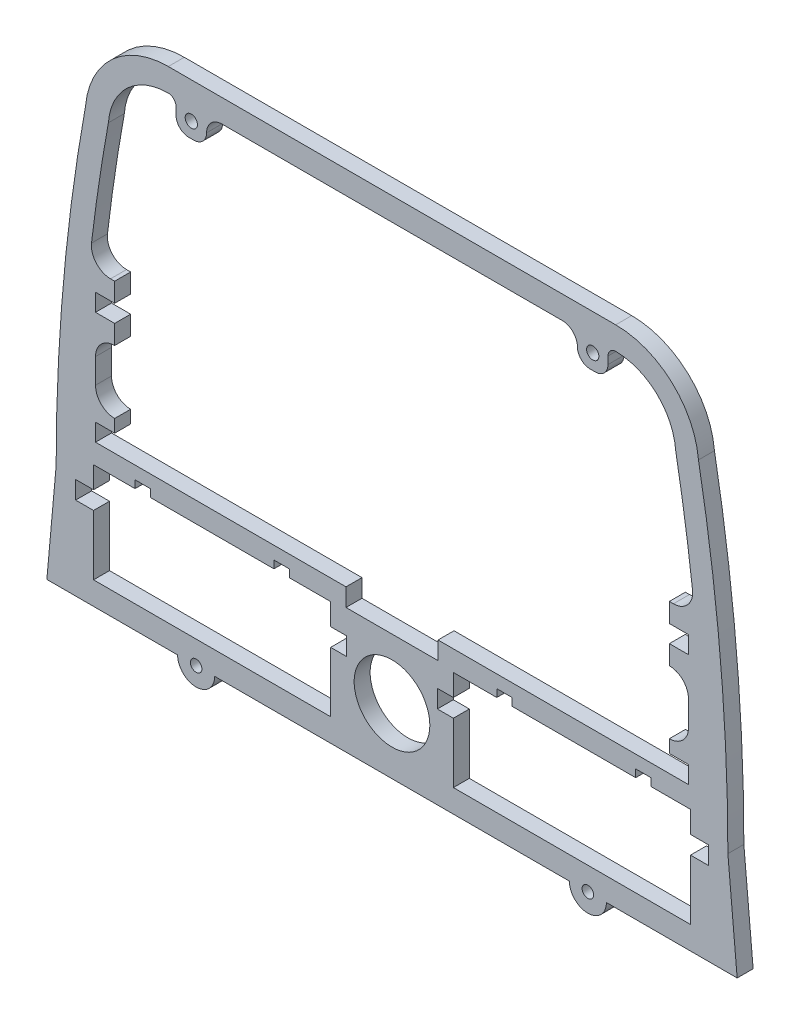
SolidWorks part; units mm, degrees
material "Delrin 2700 NC010, Low Viscosity Acetal Copolymer (SS)"
ref_plane "Front Plane" through (0, 0, 0) normal (0, 0, 1) x (1, 0, 0)
ref_plane "Top Plane" through (0, 0, 0) normal (0, 1, 0) x (1, 0, 0)
ref_plane "Right Plane" through (0, 0, 0) normal (1, 0, 0) x (0, 0, -1)
sketch "Sketch1" plane through (0, 0, 0) normal (0, 0, 1) x (1, 0, 0)
  line L0 (33.3676, -11.9888) -> (34.29, -22.225)
  line L1 (22.225, 27.94) -> (-22.225, 27.94)
  line L2 (-34.29, -22.225) -> (-30.4467, 20.4259) construction
  line L3 (-33.3676, -11.9888) -> (-33.3676, 14.6458) construction
  line L4 (-33.3676, -11.9888) -> (-34.29, -22.225)
  line L5 (16.9079, 25.654) -> (-16.9079, 25.654)
  line L6 (6.096, -13.97) -> (6.096, -19.939)
  line L7 (-29.6529, -19.939) -> (-6.096, -19.939)
  line L8 (-34.29, -22.225) -> (-21.299, -22.225)
  line L9 (-29.6529, -10.033) -> (-29.6529, -12.192)
  line L10 (18.4213, 24.1407) -> (18.4213, 24.1363)
  line L11 (19.6913, 22.8663) -> (20.1867, 22.8663)
  line L12 (21.4567, 24.1363) -> (21.4567, 24.8713)
  line L13 (-21.4567, 24.1363) -> (-21.4567, 24.8713)
  line L14 (-19.6913, 22.8663) -> (-20.1867, 22.8663)
  line L15 (-18.4213, 24.1407) -> (-18.4213, 24.1363)
  line L16 (29.4572, -8.001) -> (4.572, -8.001)
  line L17 (29.6529, -10.033) -> (25.7309, -10.033)
  line L18 (0, 18.415) -> (0, -18.415) construction
  line L19 (-1007.9925, 0) -> (48992.0075, 0) construction
  line L20 (-6.096, -10.033) -> (-10.2069, -10.033)
  line L21 (19.939, 24.384) -> (21.4567, 24.384) construction
  line L22 (6.096, -19.939) -> (29.6529, -19.939)
  line L23 (-6.096, -10.033) -> (-6.096, -12.192)
  line L24 (5.9491, -2.2098) -> (59.5431, -2.2098) construction
  line L25 (5.9491, -2.2098) -> (5.9491, -11.9888) construction
  line L26 (3.4091, -11.9888) -> (-3.4091, -11.9888) construction
  line L27 (59.5431, -2.2098) -> (59.5431, -11.9888) construction
  line L28 (-31.7887, -19.939) -> (31.7887, -19.939) construction
  line L29 (22.225, 25.654) -> (-22.225, 25.654) construction
  line L30 (-6.096, -19.939) -> (-6.1666, -19.9899)
  line L31 (29.4572, -6.2738) -> (27.5522, -6.2738)
  line L32 (27.5522, -6.2738) -> (27.5522, -5.0038)
  line L33 (-29.6529, -12.192) -> (-31.4309, -12.192)
  line L34 (27.5522, -5.0038) -> (29.4572, -5.0038)
  line L35 (29.4572, 1.27) -> (27.5522, 1.27)
  line L36 (27.5522, 1.27) -> (27.5522, 3.175)
  line L37 (27.5522, 3.175) -> (29.4572, 3.175)
  line L38 (29.4572, 4.9022) -> (27.5522, 4.9022)
  line L39 (19.939, 24.384) -> (18.4213, 24.384) construction
  line L40 (27.5522, 4.9022) -> (27.5522, 6.8072)
  line L41 (27.5522, 6.8072) -> (30.0922, 6.8072)
  line L42 (19.939, 24.384) -> (19.939, 22.8663) construction
  line L43 (6.096, -10.033) -> (6.096, -12.192)
  line L44 (-29.4572, -6.2738) -> (-29.4572, -8.001)
  line L45 (-29.4572, -6.2738) -> (-27.5522, -6.2738)
  line L46 (-27.5522, -6.2738) -> (-27.5522, -5.0038)
  line L47 (-27.5522, -5.0038) -> (-29.4572, -5.0038)
  line L48 (-29.4572, 1.27) -> (-29.4572, -5.0038)
  line L49 (-29.4572, 1.27) -> (-27.5522, 1.27)
  line L50 (-27.5522, 1.27) -> (-27.5522, 3.175)
  line L51 (-27.5522, 3.175) -> (-29.4572, 3.175)
  line L52 (-29.4572, 4.9022) -> (-29.4572, 3.175)
  line L53 (-31.4309, -12.192) -> (-31.4309, -13.97)
  line L54 (-31.4309, -13.97) -> (-29.6529, -13.97)
  line L55 (-6.096, -12.192) -> (-4.5069, -12.192)
  line L56 (-4.5069, -12.192) -> (-4.5069, -13.97)
  line L57 (-4.5069, -13.97) -> (-6.096, -13.97)
  line L58 (-29.6529, -10.033) -> (-29.6529, -19.939) construction
  line L59 (-29.6529, -14.986) -> (-33.4249, -14.986) construction
  line L60 (-29.6529, -14.986) -> (-0.4824, -14.986) construction
  line L61 (-6.096, -13.97) -> (-6.096, -19.939)
  line L62 (-29.6529, -19.939) -> (-29.6529, -13.97)
  line L63 (29.6529, -19.939) -> (29.6529, -13.97)
  line L64 (-31.0816, -12.0913) -> (-31.7887, -19.939) construction
  line L65 (29.6529, -10.033) -> (29.6529, -12.192)
  line L66 (31.4309, -13.97) -> (29.6529, -13.97)
  line L67 (31.4309, -12.192) -> (31.4309, -13.97)
  line L68 (29.6529, -12.192) -> (31.4309, -12.192)
  line L69 (6.096, -12.192) -> (4.5069, -12.192)
  line L70 (4.5069, -12.192) -> (4.5069, -13.97)
  line L71 (4.5069, -13.97) -> (6.096, -13.97)
  line L72 (29.4572, 4.9022) -> (29.4572, 3.175)
  line L73 (31.0816, -12.0913) -> (31.7887, -19.939) construction
  line L74 (29.4572, 1.27) -> (29.4572, -5.0038)
  line L75 (29.4572, -6.2738) -> (29.4572, -8.001)
  line L76 (-29.4572, 4.9022) -> (-27.5522, 4.9022)
  line L77 (-27.5522, 4.9022) -> (-27.5522, 6.8072)
  line L78 (-27.5522, 6.8072) -> (-30.0922, 6.8072)
  line L79 (-17.616, -22.225) -> (17.616, -22.225)
  line L80 (21.299, -22.225) -> (34.29, -22.225)
  line L81 (-34.29, -22.225) -> (34.29, -22.225) construction
  line L82 (-4.572, -8.001) -> (-4.572, -9.779)
  line L83 (-4.572, -9.779) -> (0, -9.779)
  line L84 (0, -9.779) -> (4.572, -9.779)
  line L85 (4.572, -9.779) -> (4.572, -8.001)
  line L86 (-4.572, -8.001) -> (-29.4572, -8.001)
  line L99 (0, -32.131) -> (0, -22.225) construction
  line L115 (-11.7309, -10.033) -> (-24.0069, -10.033)
  line L117 (11.9309, -10.1918) -> (10.4069, -10.1918) construction
  line L118 (-24.0069, -10.1917) -> (-25.5309, -10.1917) construction
  line L119 (-25.5309, -10.033) -> (-29.6529, -10.033)
  line L120 (10.4069, -10.033) -> (6.096, -10.033)
  line L121 (-10.2069, -10.1918) -> (-11.7309, -10.1918) construction
  line L122 (25.7309, -10.1917) -> (24.2069, -10.1917) construction
  line L123 (24.2069, -10.033) -> (11.9309, -10.033)
  line L125 (11.9309, -10.1918) -> (10.4069, -10.1918) construction
  line L126 (-24.0069, -10.1917) -> (-25.5309, -10.1917) construction
  line L136 (-10.2069, -10.1918) -> (-11.7309, -10.1918) construction
  line L137 (25.7309, -10.1917) -> (24.2069, -10.1917) construction
  line L138 (-25.5309, -10.1917) -> (-25.5309, -9.271)
  line L139 (-25.5309, -9.271) -> (-24.0069, -9.271)
  line L140 (-24.0069, -9.271) -> (-24.0069, -10.1917)
  line L141 (-11.7309, -10.1918) -> (-11.7309, -9.271)
  line L142 (-11.7309, -9.271) -> (-10.2069, -9.271)
  line L143 (-10.2069, -9.271) -> (-10.2069, -10.1918)
  line L144 (10.4069, -10.1918) -> (10.4069, -9.271)
  line L145 (10.4069, -9.271) -> (11.9309, -9.271)
  line L146 (11.9309, -9.271) -> (11.9309, -10.1918)
  line L147 (24.2069, -10.1917) -> (24.2069, -9.271)
  line L155 (24.2069, -9.271) -> (25.7309, -9.271)
  line L156 (25.7309, -9.271) -> (25.7309, -10.1917)
  arc A0 (22.225, 27.94) -> (30.4467, 20.4259) centre (22.225, 19.685) cw
  arc A1 (-22.225, 27.94) -> (-30.4467, 20.4259) centre (-22.225, 19.685) ccw
  arc A2 (33.3676, -11.9888) -> (30.4467, 20.4259) centre (-147.9525, -11.9888) ccw
  circle A3 centre (0, -15.748) radius 3.7592
  circle A4 centre (19.4575, -22.225) radius 0.5715
  arc A5 (-33.3676, -11.9888) -> (-30.4467, 20.4259) centre (147.9525, -11.9888) cw
  arc A6 (-17.616, -22.225) -> (-21.299, -22.225) centre (-19.4575, -22.225) cw
  arc A7 (17.616, -22.225) -> (21.299, -22.225) centre (19.4575, -22.225) ccw
  arc A8 (20.1867, 22.8663) -> (21.4567, 24.1363) centre (20.1867, 24.1363) ccw
  circle A9 centre (-19.939, 24.384) radius 0.6096
  circle A10 centre (19.939, 24.384) radius 0.6096
  arc A11 (18.4213, 24.1363) -> (19.6913, 22.8663) centre (19.6913, 24.1363) ccw
  circle A12 centre (-19.4575, -22.225) radius 0.5715
  arc A13 (18.4213, 24.1407) -> (16.9079, 25.654) centre (16.9079, 24.1407) ccw
  arc A14 (22.2416, 25.654) -> (21.4567, 24.8713) centre (22.2394, 24.8713) ccw
  arc A15 (-22.2416, 25.654) -> (-21.4567, 24.8713) centre (-22.2394, 24.8713) cw
  arc A16 (-20.1867, 22.8663) -> (-21.4567, 24.1363) centre (-20.1867, 24.1363) cw
  arc A17 (-18.4213, 24.1363) -> (-19.6913, 22.8663) centre (-19.6913, 24.1363) cw
  arc A18 (-22.2416, 25.654) -> (-28.1777, 20.1262) centre (-22.225, 19.685) ccw
  arc A19 (-18.4213, 24.1407) -> (-16.9079, 25.654) centre (-16.9079, 24.1407) cw
  arc A20 (31.0816, -12.0913) -> (31.0816, -11.9888) centre (-147.9525, -11.9888) ccw
  circle A21 centre (-19.4575, -22.225) radius 1.8415 construction
  arc A23 (22.2416, 25.654) -> (28.1777, 20.1262) centre (22.225, 19.685) cw
  arc A25 (-22.225, 25.654) -> (-28.1777, 20.1262) centre (-22.225, 19.685) ccw construction
  arc A26 (22.225, 25.654) -> (28.1777, 20.1262) centre (22.225, 19.685) cw construction
  arc A28 (-31.0816, -12.0913) -> (-28.1777, 20.1262) centre (147.9525, -11.9888) cw construction
  arc A30 (31.0816, -12.0913) -> (28.1777, 20.1262) centre (-147.9525, -11.9888) ccw construction
  arc A31 (30.0922, 6.8072) -> (28.1777, 20.1262) centre (-147.9525, -11.9888) ccw
  arc A33 (-30.0922, 6.8072) -> (-28.1777, 20.1262) centre (147.9525, -11.9888) cw
  point P0 (0, 0)
  point P1 (0, 27.94)
  point P31 (0, -11.9888)
  point P121 (-30.9018, -14.986)
  point P135 (-17.616, -22.225)
  point P160 (-15.7485, -22.098)
  point P161 (-15.7485, -28.448)
  point P166 (15.7485, -28.448)
  point P167 (15.7485, -22.098)
  dimension "D4" = 2.286
  dimension "D6" = 8.255
  dimension "D7" = 19.4575
  dimension "D8" = 50.165
  dimension "D9" = 15.748
  dimension "D5" = 1.2192
  dimension "D17" = 1.143
  dimension "D3" = 7.5184
  dimension "D18" = 1.27
  dimension "D19" = 1.27
  dimension "D26" = 11.176
  dimension "D28" = 0.7827
  dimension "D29" = 1.5133
  dimension "D32" = 1.778
  dimension "D2" = 44.45
  dimension "D10" = 1.27
  dimension "D11" = 1.27
  dimension "D12" = 68.58
  dimension "D13" = 19.939
  dimension "D14" = 22.225
  dimension "D15" = 53.594
  dimension "D16" = 9.779
  dimension "D20" = 6.096
  dimension "D21" = 11.938
  dimension "D22" = 2.032
  dimension "D23" = 1.7272
  dimension "D24" = 1.27
  dimension "D25" = 1.905
  dimension "D27" = 0.4954
  dimension "D30" = 1.905
  dimension "D31" = 1.7272
  dimension "D33" = 1.778
  dimension "D34" = 2.159
  dimension "D35" = 23.5569
  dimension "D36" = 26.924
  dimension "D37" = 1.905
  dimension "D38" = 2.54
  dimension "D39" = 1.778
  dimension "D40" = 9.144
  dimension "D42" = 0.762
extrude "Boss-Extrude1" add sketch "Sketch1" along normal blind 1.5875 contours L8 A12 A4 L0 A2 A0 L1 A1 A5 L4 L74 L16 A18 A15 L13 A16 L14 A17 L15 A19 L5 A13 L10 A11 L11 A8 L12 A14 A23 A20 L22 L43 L17 A10 A9 A3 L20 region at (32.9716, -17.1841, 0)
ref_axis "Axis1" through (0, -15.748, 0) along (0, 0, 1)
fillet "Fillet2" radius 1.905 6 edges at (-29.4572, 1.27, 0.7937) (-29.4572, -5.0038, 0.7937) (-30.0922, 6.8072, 0.7937) (29.4572, -5.0038, 0.7937) (29.4572, 1.27, 0.7937) (30.0922, 6.8072, 0.7937)
